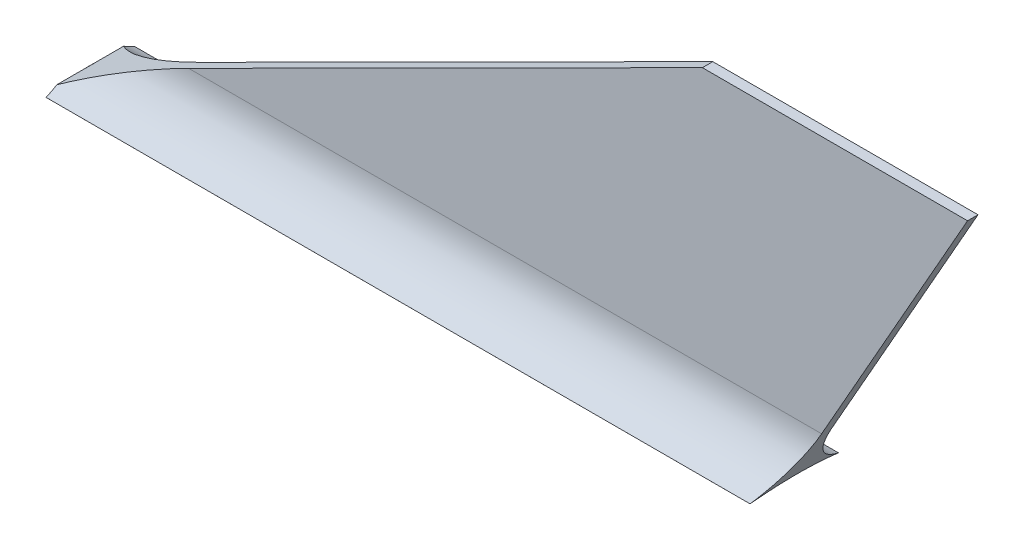
SolidWorks part; units mm, degrees
material "E-Glass Fiber"
ref_plane "Front Plane" through (0, 0, 0) normal (0, 0, 1) x (1, 0, 0)
ref_plane "Top Plane" through (0, 0, 0) normal (0, 1, 0) x (1, 0, 0)
ref_plane "Right Plane" through (0, 0, 0) normal (1, 0, 0) x (0, 0, -1)
sketch "Sketch1" plane through (0, 0, 0) normal (0, 0, 1) x (1, 0, 0)
  line L0 (0, 0) -> (0, 88.9) construction
  line L1 (0, 88.9) -> (177.3936, 88.9) construction
  line L2 (0, 0) -> (177.3936, 88.9)
  line L3 (177.3936, 88.9) -> (253.5936, 88.9)
  line L4 (253.5936, 88.9) -> (203.2, 0)
  line L5 (203.2, 0) -> (127, 0)
  line L6 (127, 0) -> (127, -12.7)
  line L7 (127, -12.7) -> (76.9874, -12.7)
  line L8 (76.9874, -12.7) -> (76.9874, 0)
  line L9 (76.9874, 0) -> (0, 0)
  dimension "D1" = 88.9
  dimension "D2" = 177.3936
  dimension "D3" = 76.2
  dimension "D4" = 203.2
  dimension "D5" = 50.0126
  dimension "D6" = 12.7
  dimension "D7" = 76.2
extrude "Boss-Extrude1" add sketch "Sketch1" along normal blind 2.9972
sketch "Sketch2" plane through (0, 0, 0) normal (1, 0, 0) x (0, 0, -1)
  arc A0 (-14.1986, -1.591) -> (11.2014, -1.591) centre (-1.4986, -50.7779) cw
  point P3 (-1.4986, 0.0221)
  dimension "D1" = 50.8
  dimension "D2" = 25.4
extrude "Extrude-Thin1" add sketch "Sketch2" along normal up to surface (202.2967 mm away) thin up to face at (228.3968, 44.45, 1.4986) thin type one direction wall 0.0025
fillet "Fillet1" radius 17.78 2 edges at (101.6, 0, 0) (101.6, 0, 2.9972)
